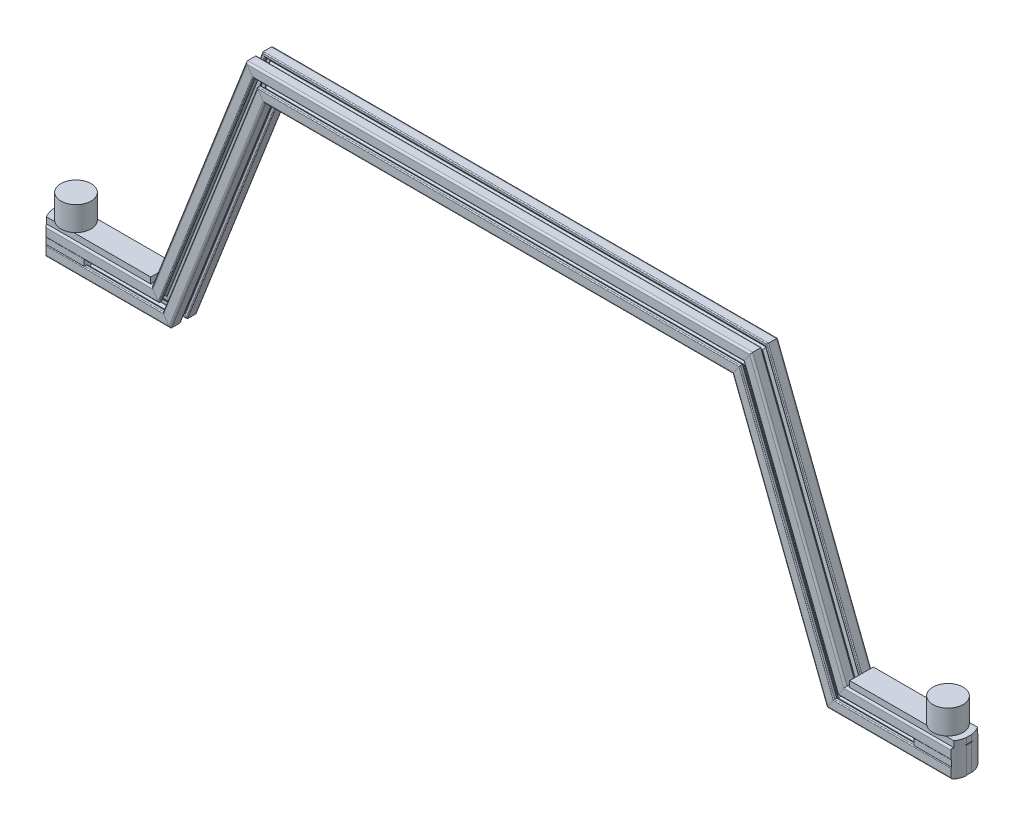
SolidWorks part; units mm, degrees
material "Commercially Pure CP-Ti UNS R50400 (SS)"
ref_plane "Front Plane" through (0, 0, 0) normal (0, 0, 1) x (1, 0, 0)
ref_plane "Top Plane" through (0, 0, 0) normal (0, 1, 0) x (1, 0, 0)
ref_plane "Right Plane" through (0, 0, 0) normal (1, 0, 0) x (0, 0, -1)
sketch "Sketch7" plane through (0, 0, 0) normal (1, 0, 0) x (0, 0, -1)
  line L0 (13.9698, 21.2743) -> (13.5298, 21.2743)
  line L1 (12.0298, 22.7743) -> (12.0298, 23.2743)
  line L2 (13.5298, 24.7743) -> (23.1398, 24.7743)
  line L3 (25.4198, 22.4943) -> (25.4198, 12.8843)
  line L4 (23.9198, 11.3843) -> (23.4198, 11.3843)
  line L5 (21.9198, 12.8843) -> (21.9198, 13.3243)
  line L6 (20.9198, 14.3243) -> (15.3498, 14.3243)
  line L7 (14.9698, 14.7043) -> (14.9698, 20.2743)
  line L8 (21.9589, -6.6897) -> (21.9589, -6.2497)
  line L9 (23.4589, -4.7497) -> (23.9589, -4.7497)
  line L10 (25.4589, -6.2497) -> (25.4589, -15.8597)
  line L11 (23.1789, -18.1397) -> (13.5689, -18.1397)
  line L12 (12.0689, -16.6397) -> (12.0689, -16.1397)
  line L13 (13.5689, -14.6397) -> (14.0089, -14.6397)
  line L14 (15.0089, -13.6397) -> (15.0089, -8.0697)
  line L15 (15.3889, -7.6897) -> (20.9589, -7.6897)
  line L16 (-6.0052, -14.6787) -> (-5.5652, -14.6787)
  line L17 (-4.0652, -16.1787) -> (-4.0652, -16.6787)
  line L18 (-5.5652, -18.1787) -> (-15.1752, -18.1787)
  line L19 (-17.4552, -15.8987) -> (-17.4552, -6.2887)
  line L20 (-15.9552, -4.7887) -> (-15.4552, -4.7887)
  line L21 (-13.9552, -6.2887) -> (-13.9552, -6.7287)
  line L22 (-12.9552, -7.7287) -> (-7.3852, -7.7287)
  line L23 (-7.0052, -8.1087) -> (-7.0052, -13.6787)
  line L24 (1.8289, -2.4886) -> (1.4132, -2.3164)
  line L25 (-1.632, 0.7289) -> (-1.8042, 1.1447)
  line L26 (-1.804, 5.4512) -> (-1.6318, 5.867)
  line L27 (1.4134, 8.9121) -> (1.8292, 9.0843)
  line L28 (6.1358, 9.0842) -> (6.5515, 8.912)
  line L29 (9.5966, 5.8667) -> (9.7688, 5.451)
  line L30 (9.7687, 1.1444) -> (9.5965, 0.7287)
  line L31 (6.5512, -2.3165) -> (6.1355, -2.4887)
  line L32 (-13.9942, 13.2853) -> (-13.9942, 12.8453)
  line L33 (-15.4942, 11.3453) -> (-15.9942, 11.3453)
  line L34 (-17.4942, 12.8453) -> (-17.4942, 22.4553)
  line L35 (-15.2142, 24.7353) -> (-5.6042, 24.7353)
  line L36 (-4.1042, 23.2353) -> (-4.1042, 22.7353)
  line L37 (-5.6042, 21.2353) -> (-6.0442, 21.2353)
  line L38 (-7.0442, 20.2353) -> (-7.0442, 14.6653)
  line L39 (-7.4242, 14.2853) -> (-12.9942, 14.2853)
  line L40 (4.9058, 11.2153) -> (4.0058, 10.7002)
  line L41 (4.0058, 10.7002) -> (3.1058, 11.2153)
  line L42 (3.1058, 11.2153) -> (-2.1975, 11.2153)
  line L43 (-2.4662, 11.3266) -> (-5.9329, 14.7933)
  line L44 (-6.0442, 15.062) -> (-6.0442, 19.3553)
  line L45 (-5.6642, 19.7353) -> (-2.5792, 19.7353)
  line L46 (-1.0592, 21.2553) -> (-1.0592, 24.2153)
  line L47 (-2.5792, 25.7353) -> (-15.4942, 25.7353)
  line L48 (-18.4942, 22.7353) -> (-18.4942, 9.8203)
  line L49 (-16.9742, 8.3003) -> (-14.0142, 8.3003)
  line L50 (-12.4942, 9.8203) -> (-12.4942, 12.9053)
  line L51 (-12.1142, 13.2853) -> (-7.8138, 13.2853)
  line L52 (-7.5451, 13.174) -> (-4.0855, 9.7144)
  line L53 (-3.9742, 9.4457) -> (-3.9742, 4.1353)
  line L54 (-3.9742, 4.1353) -> (-3.4546, 3.2353)
  line L55 (-3.4546, 3.2353) -> (-3.9742, 2.3353)
  line L56 (-3.9742, 2.3353) -> (-3.9742, -2.968)
  line L57 (-4.0855, -3.2367) -> (-7.5522, -6.7034)
  line L58 (-7.8209, -6.8147) -> (-12.1142, -6.8147)
  line L59 (-12.4942, -6.4347) -> (-12.4942, -3.3497)
  line L60 (-14.0142, -1.8297) -> (-16.9742, -1.8297)
  line L61 (-18.4942, -3.3497) -> (-18.4942, -16.2647)
  line L62 (-15.4942, -19.2647) -> (-2.5792, -19.2647)
  line L63 (-1.0592, -17.7447) -> (-1.0592, -14.7847)
  line L64 (-2.5792, -13.2647) -> (-5.6642, -13.2647)
  line L65 (-6.0442, -12.8847) -> (-6.0442, -8.5843)
  line L66 (-5.9329, -8.3156) -> (-2.4733, -4.856)
  line L67 (-2.2046, -4.7447) -> (3.1058, -4.7447)
  line L68 (3.1058, -4.7447) -> (4.0058, -4.2295)
  line L69 (4.0058, -4.2295) -> (4.9058, -4.7447)
  line L70 (4.9058, -4.7447) -> (10.2091, -4.7447)
  line L71 (10.4778, -4.856) -> (13.9445, -8.3227)
  line L72 (14.0558, -8.5914) -> (14.0558, -12.8847)
  line L73 (13.6758, -13.2647) -> (10.5908, -13.2647)
  line L74 (9.0708, -14.7847) -> (9.0708, -17.7447)
  line L75 (10.5908, -19.2647) -> (23.5058, -19.2647)
  line L76 (26.5058, -16.2647) -> (26.5058, -3.3497)
  line L77 (24.9858, -1.8297) -> (22.0258, -1.8297)
  line L78 (20.5058, -3.3497) -> (20.5058, -6.4347)
  line L79 (20.1258, -6.8147) -> (15.8254, -6.8147)
  line L80 (15.5567, -6.7034) -> (12.0971, -3.2438)
  line L81 (11.9858, -2.9751) -> (11.9858, 2.3353)
  line L82 (11.9858, 2.3353) -> (11.4662, 3.2353)
  line L83 (11.4662, 3.2353) -> (11.9858, 4.1353)
  line L84 (11.9858, 4.1353) -> (11.9858, 9.4386)
  line L85 (12.0971, 9.7073) -> (15.5638, 13.174)
  line L86 (15.8325, 13.2853) -> (20.1258, 13.2853)
  line L87 (20.5058, 12.9053) -> (20.5058, 9.8203)
  line L88 (22.0258, 8.3003) -> (24.9858, 8.3003)
  line L89 (26.5058, 9.8203) -> (26.5058, 22.7353)
  line L90 (23.5058, 25.7353) -> (10.5908, 25.7353)
  line L91 (9.0708, 24.2153) -> (9.0708, 21.2553)
  line L92 (10.5908, 19.7353) -> (13.6758, 19.7353)
  line L93 (14.0558, 19.3553) -> (14.0558, 15.0549)
  line L94 (13.9445, 14.7862) -> (10.4849, 11.3266)
  line L95 (10.2162, 11.2153) -> (4.9058, 11.2153)
  arc A0 (14.9698, 20.2743) -> (13.9698, 21.2743) centre (13.9698, 20.2743) ccw
  arc A1 (12.0298, 22.7743) -> (13.5298, 21.2743) centre (13.5298, 22.7743) ccw
  arc A2 (13.5298, 24.7743) -> (12.0298, 23.2743) centre (13.5298, 23.2743) ccw
  arc A3 (25.4198, 22.4943) -> (23.1398, 24.7743) centre (23.1398, 22.4943) ccw
  arc A4 (23.9198, 11.3843) -> (25.4198, 12.8843) centre (23.9198, 12.8843) ccw
  arc A5 (21.9198, 12.8843) -> (23.4198, 11.3843) centre (23.4198, 12.8843) ccw
  arc A6 (21.9198, 13.3243) -> (20.9198, 14.3243) centre (20.9198, 13.3243) ccw
  arc A7 (14.9698, 14.7043) -> (15.3498, 14.3243) centre (15.3498, 14.7043) ccw
  arc A8 (20.9589, -7.6897) -> (21.9589, -6.6897) centre (20.9589, -6.6897) ccw
  arc A9 (23.4589, -4.7497) -> (21.9589, -6.2497) centre (23.4589, -6.2497) ccw
  arc A10 (25.4589, -6.2497) -> (23.9589, -4.7497) centre (23.9589, -6.2497) ccw
  arc A11 (23.1789, -18.1397) -> (25.4589, -15.8597) centre (23.1789, -15.8597) ccw
  arc A12 (12.0689, -16.6397) -> (13.5689, -18.1397) centre (13.5689, -16.6397) ccw
  arc A13 (13.5689, -14.6397) -> (12.0689, -16.1397) centre (13.5689, -16.1397) ccw
  arc A14 (14.0089, -14.6397) -> (15.0089, -13.6397) centre (14.0089, -13.6397) ccw
  arc A15 (15.3889, -7.6897) -> (15.0089, -8.0697) centre (15.3889, -8.0697) ccw
  arc A16 (-7.0052, -13.6787) -> (-6.0052, -14.6787) centre (-6.0052, -13.6787) ccw
  arc A17 (-4.0652, -16.1787) -> (-5.5652, -14.6787) centre (-5.5652, -16.1787) ccw
  arc A18 (-5.5652, -18.1787) -> (-4.0652, -16.6787) centre (-5.5652, -16.6787) ccw
  arc A19 (-17.4552, -15.8987) -> (-15.1752, -18.1787) centre (-15.1752, -15.8987) ccw
  arc A20 (-15.9552, -4.7887) -> (-17.4552, -6.2887) centre (-15.9552, -6.2887) ccw
  arc A21 (-13.9552, -6.2887) -> (-15.4552, -4.7887) centre (-15.4552, -6.2887) ccw
  arc A22 (-13.9552, -6.7287) -> (-12.9552, -7.7287) centre (-12.9552, -6.7287) ccw
  arc A23 (-7.0052, -8.1087) -> (-7.3852, -7.7287) centre (-7.3852, -8.1087) ccw
  arc A24 (1.0363, -0.7421) -> (1.4132, -2.3164) centre (1.7959, -1.3925) ccw
  arc A25 (-0.0577, 0.352) -> (1.0363, -0.7421) centre (3.9823, 3.2978) ccw
  arc A26 (-1.632, 0.7289) -> (-0.0577, 0.352) centre (-0.7081, 1.1116) ccw
  arc A27 (-0.9575, 2.5244) -> (-1.8042, 1.1447) centre (-0.8803, 1.5274) ccw
  arc A28 (-0.9574, 4.0715) -> (-0.9575, 2.5244) centre (3.9823, 3.2978) ccw
  arc A29 (-1.804, 5.4512) -> (-0.9574, 4.0715) centre (-0.8802, 5.0686) ccw
  arc A30 (-0.0575, 6.2439) -> (-1.6318, 5.867) centre (-0.708, 5.4843) ccw
  arc A31 (1.0365, 7.3379) -> (-0.0575, 6.2439) centre (3.9823, 3.2978) ccw
  arc A32 (1.4134, 8.9121) -> (1.0365, 7.3379) centre (1.7961, 7.9882) ccw
  arc A33 (3.2089, 8.2376) -> (1.8292, 9.0843) centre (2.2119, 8.1604) ccw
  arc A34 (4.7561, 8.2376) -> (3.2089, 8.2376) centre (3.9823, 3.2978) ccw
  arc A35 (6.1358, 9.0842) -> (4.7561, 8.2376) centre (5.7531, 8.1603) ccw
  arc A36 (6.9284, 7.3377) -> (6.5515, 8.912) centre (6.1688, 7.9881) ccw
  arc A37 (8.0224, 6.2437) -> (6.9284, 7.3377) centre (3.9823, 3.2978) ccw
  arc A38 (9.5966, 5.8667) -> (8.0224, 6.2437) centre (8.6727, 5.484) ccw
  arc A39 (8.9222, 4.0713) -> (9.7688, 5.451) centre (8.845, 5.0683) ccw
  arc A40 (8.9221, 2.5241) -> (8.9222, 4.0713) centre (3.9823, 3.2978) ccw
  arc A41 (9.7687, 1.1444) -> (8.9221, 2.5241) centre (8.8448, 1.5271) ccw
  arc A42 (8.0222, 0.3518) -> (9.5965, 0.7287) centre (8.6726, 1.1113) ccw
  arc A43 (6.9282, -0.7422) -> (8.0222, 0.3518) centre (3.9823, 3.2978) ccw
  arc A44 (6.5512, -2.3165) -> (6.9282, -0.7422) centre (6.1685, -1.3926) ccw
  arc A45 (4.7558, -1.642) -> (6.1355, -2.4887) centre (5.7528, -1.5648) ccw
  arc A46 (3.2086, -1.642) -> (4.7558, -1.642) centre (3.9823, 3.2978) ccw
  arc A47 (1.8289, -2.4886) -> (3.2086, -1.642) centre (2.2116, -1.5647) ccw
  arc A48 (-12.9942, 14.2853) -> (-13.9942, 13.2853) centre (-12.9942, 13.2853) ccw
  arc A49 (-15.4942, 11.3453) -> (-13.9942, 12.8453) centre (-15.4942, 12.8453) ccw
  arc A50 (-17.4942, 12.8453) -> (-15.9942, 11.3453) centre (-15.9942, 12.8453) ccw
  arc A51 (-15.2142, 24.7353) -> (-17.4942, 22.4553) centre (-15.2142, 22.4553) ccw
  arc A52 (-4.1042, 23.2353) -> (-5.6042, 24.7353) centre (-5.6042, 23.2353) ccw
  arc A53 (-5.6042, 21.2353) -> (-4.1042, 22.7353) centre (-5.6042, 22.7353) ccw
  arc A54 (-6.0442, 21.2353) -> (-7.0442, 20.2353) centre (-6.0442, 20.2353) ccw
  arc A55 (-7.4242, 14.2853) -> (-7.0442, 14.6653) centre (-7.4242, 14.6653) ccw
  arc A56 (-2.4662, 11.3266) -> (-2.1975, 11.2153) centre (-2.1975, 11.5953) ccw
  arc A57 (-6.0442, 15.062) -> (-5.9329, 14.7933) centre (-5.6642, 15.062) ccw
  arc A58 (-5.6642, 19.7353) -> (-6.0442, 19.3553) centre (-5.6642, 19.3553) ccw
  arc A59 (-2.5792, 19.7353) -> (-1.0592, 21.2553) centre (-2.5792, 21.2553) ccw
  arc A60 (-1.0592, 24.2153) -> (-2.5792, 25.7353) centre (-2.5792, 24.2153) ccw
  arc A61 (-15.4942, 25.7353) -> (-18.4942, 22.7353) centre (-15.4942, 22.7353) ccw
  arc A62 (-18.4942, 9.8203) -> (-16.9742, 8.3003) centre (-16.9742, 9.8203) ccw
  arc A63 (-14.0142, 8.3003) -> (-12.4942, 9.8203) centre (-14.0142, 9.8203) ccw
  arc A64 (-12.1142, 13.2853) -> (-12.4942, 12.9053) centre (-12.1142, 12.9053) ccw
  arc A65 (-7.5451, 13.174) -> (-7.8138, 13.2853) centre (-7.8138, 12.9053) ccw
  arc A66 (-3.9742, 9.4457) -> (-4.0855, 9.7144) centre (-4.3542, 9.4457) ccw
  arc A67 (-4.0855, -3.2367) -> (-3.9742, -2.968) centre (-4.3542, -2.968) ccw
  arc A68 (-7.8209, -6.8147) -> (-7.5522, -6.7034) centre (-7.8209, -6.4347) ccw
  arc A69 (-12.4942, -6.4347) -> (-12.1142, -6.8147) centre (-12.1142, -6.4347) ccw
  arc A70 (-12.4942, -3.3497) -> (-14.0142, -1.8297) centre (-14.0142, -3.3497) ccw
  arc A71 (-16.9742, -1.8297) -> (-18.4942, -3.3497) centre (-16.9742, -3.3497) ccw
  arc A72 (-18.4942, -16.2647) -> (-15.4942, -19.2647) centre (-15.4942, -16.2647) ccw
  arc A73 (-2.5792, -19.2647) -> (-1.0592, -17.7447) centre (-2.5792, -17.7447) ccw
  arc A74 (-1.0592, -14.7847) -> (-2.5792, -13.2647) centre (-2.5792, -14.7847) ccw
  arc A75 (-6.0442, -12.8847) -> (-5.6642, -13.2647) centre (-5.6642, -12.8847) ccw
  arc A76 (-5.9329, -8.3156) -> (-6.0442, -8.5843) centre (-5.6642, -8.5843) ccw
  arc A77 (-2.2046, -4.7447) -> (-2.4733, -4.856) centre (-2.2046, -5.1247) ccw
  arc A78 (10.4778, -4.856) -> (10.2091, -4.7447) centre (10.2091, -5.1247) ccw
  arc A79 (14.0558, -8.5914) -> (13.9445, -8.3227) centre (13.6758, -8.5914) ccw
  arc A80 (13.6758, -13.2647) -> (14.0558, -12.8847) centre (13.6758, -12.8847) ccw
  arc A81 (10.5908, -13.2647) -> (9.0708, -14.7847) centre (10.5908, -14.7847) ccw
  arc A82 (9.0708, -17.7447) -> (10.5908, -19.2647) centre (10.5908, -17.7447) ccw
  arc A83 (23.5058, -19.2647) -> (26.5058, -16.2647) centre (23.5058, -16.2647) ccw
  arc A84 (26.5058, -3.3497) -> (24.9858, -1.8297) centre (24.9858, -3.3497) ccw
  arc A85 (22.0258, -1.8297) -> (20.5058, -3.3497) centre (22.0258, -3.3497) ccw
  arc A86 (20.1258, -6.8147) -> (20.5058, -6.4347) centre (20.1258, -6.4347) ccw
  arc A87 (15.5567, -6.7034) -> (15.8254, -6.8147) centre (15.8254, -6.4347) ccw
  arc A88 (11.9858, -2.9751) -> (12.0971, -3.2438) centre (12.3658, -2.9751) ccw
  arc A89 (12.0971, 9.7073) -> (11.9858, 9.4386) centre (12.3658, 9.4386) ccw
  arc A90 (15.8325, 13.2853) -> (15.5638, 13.174) centre (15.8325, 12.9053) ccw
  arc A91 (20.5058, 12.9053) -> (20.1258, 13.2853) centre (20.1258, 12.9053) ccw
  arc A92 (20.5058, 9.8203) -> (22.0258, 8.3003) centre (22.0258, 9.8203) ccw
  arc A93 (24.9858, 8.3003) -> (26.5058, 9.8203) centre (24.9858, 9.8203) ccw
  arc A94 (26.5058, 22.7353) -> (23.5058, 25.7353) centre (23.5058, 22.7353) ccw
  arc A95 (10.5908, 25.7353) -> (9.0708, 24.2153) centre (10.5908, 24.2153) ccw
  arc A96 (9.0708, 21.2553) -> (10.5908, 19.7353) centre (10.5908, 21.2553) ccw
  arc A97 (14.0558, 19.3553) -> (13.6758, 19.7353) centre (13.6758, 19.3553) ccw
  arc A98 (13.9445, 14.7862) -> (14.0558, 15.0549) centre (13.6758, 15.0549) ccw
  arc A99 (10.2162, 11.2153) -> (10.4849, 11.3266) centre (10.2162, 11.5953) ccw
sketch "Sketch1" plane through (0, 0, 0) normal (0, 0, 1) x (1, 0, 0)
  line L0 (0, 0) -> (200, 0)
  line L1 (200, 0) -> (355.8974, 400)
  line L2 (355.8974, 400) -> (755.8974, 400)
  dimension "D1" = 400
  dimension "D2" = 200
  dimension "D3" = 400
sketch "Sketch2" [suppressed] plane through (0, 0, 0) normal (1, 0, 0) x (0, 0, -1)
  line L0 (-33.5, -41) -> (-31.5, -41)
  line L1 (-31.5, -43) -> (-42, -43)
  line L2 (-43, -42) -> (-43, -31.5)
  line L3 (-41, -31.5) -> (-41, -33.5)
  line L4 (-40, -34.5) -> (-34.88, -34.5)
  line L5 (-34.5, -34.88) -> (-34.5, -40)
  line L6 (-16.657, -26.2238) -> (-18.284, -25.188)
  line L7 (-19.8123, -26.7162) -> (-18.7764, -28.3429)
  line L8 (-21.0015, -29.2647) -> (-21.4195, -27.3819)
  line L9 (-23.5808, -27.3818) -> (-23.9986, -29.2645)
  line L10 (-26.2238, -28.343) -> (-25.188, -26.716)
  line L11 (-26.7162, -25.1877) -> (-28.3429, -26.2236)
  line L12 (-29.2647, -23.9985) -> (-27.3819, -23.5805)
  line L13 (-27.3818, -21.4192) -> (-29.2645, -21.0014)
  line L14 (-28.343, -18.7762) -> (-26.716, -19.812)
  line L15 (-25.1877, -18.2838) -> (-26.2236, -16.6571)
  line L16 (-23.9985, -15.7353) -> (-23.5805, -17.6181)
  line L17 (-21.4192, -17.6182) -> (-21.0014, -15.7355)
  line L18 (-18.7762, -16.657) -> (-19.812, -18.284)
  line L19 (-18.2838, -19.8123) -> (-16.6571, -18.7764)
  line L20 (-15.7353, -21.0015) -> (-17.6181, -21.4195)
  line L21 (-17.6182, -23.5808) -> (-15.7355, -23.9986)
  line L22 (41, -33.5) -> (41, -31.5)
  line L23 (43, -31.5) -> (43, -42)
  line L24 (42, -43) -> (31.5, -43)
  line L25 (31.5, -41) -> (33.5, -41)
  line L26 (34.5, -40) -> (34.5, -34.88)
  line L27 (34.88, -34.5) -> (40, -34.5)
  line L28 (26.7162, -19.8123) -> (28.3429, -18.7764)
  line L29 (29.2647, -21.0015) -> (27.3819, -21.4195)
  line L30 (27.3818, -23.5808) -> (29.2645, -23.9986)
  line L31 (28.343, -26.2238) -> (26.716, -25.188)
  line L32 (25.1877, -26.7162) -> (26.2236, -28.3429)
  line L33 (23.9985, -29.2647) -> (23.5805, -27.3819)
  line L34 (21.4192, -27.3818) -> (21.0014, -29.2645)
  line L35 (18.7762, -28.343) -> (19.812, -26.716)
  line L36 (18.2838, -25.1877) -> (16.6571, -26.2236)
  line L37 (15.7353, -23.9985) -> (17.6181, -23.5805)
  line L38 (17.6182, -21.4192) -> (15.7355, -21.0014)
  line L39 (16.657, -18.7762) -> (18.284, -19.812)
  line L40 (19.8123, -18.2838) -> (18.7764, -16.6571)
  line L41 (21.0015, -15.7353) -> (21.4195, -17.6181)
  line L42 (23.5808, -17.6182) -> (23.9986, -15.7355)
  line L43 (26.2238, -16.657) -> (25.188, -18.284)
  line L44 (34.5, 34.88) -> (34.5, 40)
  line L45 (33.5, 41) -> (31.5, 41)
  line L46 (31.5, 43) -> (42, 43)
  line L47 (43, 42) -> (43, 31.5)
  line L48 (41, 31.5) -> (41, 33.5)
  line L49 (40, 34.5) -> (34.88, 34.5)
  line L50 (26.7162, 25.1877) -> (28.3429, 26.2236)
  line L51 (29.2647, 23.9985) -> (27.3819, 23.5805)
  line L52 (27.3818, 21.4192) -> (29.2645, 21.0014)
  line L53 (28.343, 18.7762) -> (26.716, 19.812)
  line L54 (25.1877, 18.2838) -> (26.2236, 16.6571)
  line L55 (23.9985, 15.7353) -> (23.5805, 17.6181)
  line L56 (21.4192, 17.6182) -> (21.0014, 15.7355)
  line L57 (18.7762, 16.657) -> (19.812, 18.284)
  line L58 (18.2838, 19.8123) -> (16.6571, 18.7764)
  line L59 (15.7353, 21.0015) -> (17.6181, 21.4195)
  line L60 (17.6182, 23.5808) -> (15.7355, 23.9986)
  line L61 (16.657, 26.2238) -> (18.284, 25.188)
  line L62 (19.8123, 26.7162) -> (18.7764, 28.3429)
  line L63 (21.0015, 29.2647) -> (21.4195, 27.3819)
  line L64 (23.5808, 27.3818) -> (23.9986, 29.2645)
  line L65 (26.2238, 28.343) -> (25.188, 26.716)
  line L66 (-41, 33.5) -> (-41, 31.5)
  line L67 (-43, 31.5) -> (-43, 42)
  line L68 (-42, 43) -> (-31.5, 43)
  line L69 (-31.5, 41) -> (-33.5, 41)
  line L70 (-34.5, 40) -> (-34.5, 34.88)
  line L71 (-34.88, 34.5) -> (-40, 34.5)
  line L72 (-16.657, 18.7762) -> (-18.284, 19.812)
  line L73 (-19.8123, 18.2838) -> (-18.7764, 16.6571)
  line L74 (-21.0015, 15.7353) -> (-21.4195, 17.6181)
  line L75 (-23.5808, 17.6182) -> (-23.9986, 15.7355)
  line L76 (-26.2238, 16.657) -> (-25.188, 18.284)
  line L77 (-26.7162, 19.8123) -> (-28.3429, 18.7764)
  line L78 (-29.2647, 21.0015) -> (-27.3819, 21.4195)
  line L79 (-27.3818, 23.5808) -> (-29.2645, 23.9986)
  line L80 (-28.343, 26.2238) -> (-26.716, 25.188)
  line L81 (-25.1877, 26.7162) -> (-26.2236, 28.3429)
  line L82 (-23.9985, 29.2647) -> (-23.5805, 27.3819)
  line L83 (-21.4192, 27.3818) -> (-21.0014, 29.2645)
  line L84 (-18.7762, 28.343) -> (-19.812, 26.716)
  line L85 (-18.2838, 25.1877) -> (-16.6571, 26.2236)
  line L86 (-15.7353, 23.9985) -> (-17.6181, 23.5805)
  line L87 (-17.6182, 21.4192) -> (-15.7355, 21.0014)
  line L88 (39, -10.16) -> (33.3774, -10.16)
  line L89 (31.9632, -10.7458) -> (29.8203, -12.8887)
  line L90 (29.5516, -13) -> (23.4, -13)
  line L91 (23.4, -13) -> (22.5, -13.5151)
  line L92 (22.5, -13.5151) -> (21.6, -13)
  line L93 (21.6, -13) -> (15, -13)
  line L94 (13, -15) -> (13, -21.6)
  line L95 (13, -21.6) -> (13.5196, -22.5)
  line L96 (13.5196, -22.5) -> (13, -23.4)
  line L97 (13, -23.4) -> (13, -29.5516)
  line L98 (12.8887, -29.8203) -> (11.3787, -31.3303)
  line L99 (10.5, -33.4516) -> (10.5, -40)
  line L100 (11.5, -41) -> (13.5, -41)
  line L101 (13.5, -43) -> (-13.5, -43)
  line L102 (-13.5, -41) -> (-11.5, -41)
  line L103 (-10.5, -40) -> (-10.5, -33.4516)
  line L104 (-11.3787, -31.3303) -> (-12.8887, -29.8203)
  line L105 (-13, -29.5516) -> (-13, -23.4)
  line L106 (-13, -23.4) -> (-13.5196, -22.5)
  line L107 (-13.5196, -22.5) -> (-13, -21.6)
  line L108 (-13, -21.6) -> (-13, -15)
  line L109 (-15, -13) -> (-21.6, -13)
  line L110 (-21.6, -13) -> (-22.5, -13.5151)
  line L111 (-22.5, -13.5151) -> (-23.4, -13)
  line L112 (-23.4, -13) -> (-29.5516, -13)
  line L113 (-29.8203, -12.8887) -> (-31.9632, -10.7458)
  line L114 (-33.3774, -10.16) -> (-39, -10.16)
  line L115 (-41, -12.16) -> (-41, -13.5)
  line L116 (-43, -13.5) -> (-43, 13.5)
  line L117 (-41, 13.5) -> (-41, 12.16)
  line L118 (-39, 10.16) -> (-33.3774, 10.16)
  line L119 (-31.9632, 10.7458) -> (-29.8203, 12.8887)
  line L120 (-29.5516, 13) -> (-23.4, 13)
  line L121 (-23.4, 13) -> (-22.5, 13.5151)
  line L122 (-22.5, 13.5151) -> (-21.6, 13)
  line L123 (-21.6, 13) -> (-15, 13)
  line L124 (-13, 15) -> (-13, 21.6)
  line L125 (-13, 21.6) -> (-13.5196, 22.5)
  line L126 (-13.5196, 22.5) -> (-13, 23.4)
  line L127 (-13, 23.4) -> (-13, 29.5516)
  line L128 (-12.8887, 29.8203) -> (-11.3787, 31.3303)
  line L129 (-10.5, 33.4516) -> (-10.5, 40)
  line L130 (-11.5, 41) -> (-13.5, 41)
  line L131 (-13.5, 43) -> (13.5, 43)
  line L132 (13.5, 41) -> (11.5, 41)
  line L133 (10.5, 40) -> (10.5, 33.4516)
  line L134 (11.3787, 31.3303) -> (12.8887, 29.8203)
  line L135 (13, 29.5516) -> (13, 23.4)
  line L136 (13, 23.4) -> (13.5196, 22.5)
  line L137 (13.5196, 22.5) -> (13, 21.6)
  line L138 (13, 21.6) -> (13, 15)
  line L139 (15, 13) -> (21.6, 13)
  line L140 (21.6, 13) -> (22.5, 13.5151)
  line L141 (22.5, 13.5151) -> (23.4, 13)
  line L142 (23.4, 13) -> (29.5516, 13)
  line L143 (29.8203, 12.8887) -> (31.9581, 10.7509)
  line L144 (33.3723, 10.1651) -> (39, 10.1651)
  line L145 (41, 12.1651) -> (41, 13.5)
  line L146 (43, 13.5) -> (43, -13.5)
  line L147 (41, -13.5) -> (41, -12.16)
  line L148 (45, -15.915) -> (45, 15.915)
  line L149 (43.48, 17.435) -> (40.52, 17.435)
  line L150 (39, 15.915) -> (39, 13.45)
  line L151 (38, 12.45) -> (34.9984, 12.45)
  line L152 (34.7297, 12.5613) -> (32.1113, 15.1797)
  line L153 (32, 15.4484) -> (32, 21.6)
  line L154 (32, 21.6) -> (31.4804, 22.5)
  line L155 (31.4804, 22.5) -> (32, 23.4)
  line L156 (32, 23.4) -> (32, 29.5516)
  line L157 (32.1113, 29.8203) -> (34.7297, 32.4387)
  line L158 (34.9984, 32.55) -> (38, 32.55)
  line L159 (39, 31.55) -> (39, 29.085)
  line L160 (40.52, 27.565) -> (43.48, 27.565)
  line L161 (45, 29.085) -> (45, 42)
  line L162 (42, 45) -> (29.085, 45)
  line L163 (27.565, 43.48) -> (27.565, 40.52)
  line L164 (29.085, 39) -> (31.55, 39)
  line L165 (32.55, 38) -> (32.55, 34.9984)
  line L166 (32.4387, 34.7297) -> (29.8203, 32.1113)
  line L167 (29.5516, 32) -> (23.4, 32)
  line L168 (23.4, 32) -> (22.5, 31.4849)
  line L169 (22.5, 31.4849) -> (21.6, 32)
  line L170 (21.6, 32) -> (15.4484, 32)
  line L171 (15.1797, 32.1113) -> (12.5613, 34.7297)
  line L172 (12.45, 34.9984) -> (12.45, 38)
  line L173 (13.45, 39) -> (15.915, 39)
  line L174 (17.435, 40.52) -> (17.435, 43.48)
  line L175 (15.915, 45) -> (-15.915, 45)
  line L176 (-17.435, 43.48) -> (-17.435, 40.52)
  line L177 (-15.915, 39) -> (-13.45, 39)
  line L178 (-12.45, 38) -> (-12.45, 34.9984)
  line L179 (-12.5613, 34.7297) -> (-15.1797, 32.1113)
  line L180 (-15.4484, 32) -> (-21.6, 32)
  line L181 (-21.6, 32) -> (-22.5, 31.4849)
  line L182 (-22.5, 31.4849) -> (-23.4, 32)
  line L183 (-23.4, 32) -> (-29.5516, 32)
  line L184 (-29.8203, 32.1113) -> (-32.4387, 34.7297)
  line L185 (-32.55, 34.9984) -> (-32.55, 38)
  line L186 (-31.55, 39) -> (-29.085, 39)
  line L187 (-27.565, 40.52) -> (-27.565, 43.48)
  line L188 (-29.085, 45) -> (-42, 45)
  line L189 (-45, 42) -> (-45, 29.085)
  line L190 (-43.48, 27.565) -> (-40.52, 27.565)
  line L191 (-39, 29.085) -> (-39, 31.55)
  line L192 (-38, 32.55) -> (-34.9984, 32.55)
  line L193 (-34.7297, 32.4387) -> (-32.1113, 29.8203)
  line L194 (-32, 29.5516) -> (-32, 23.4)
  line L195 (-32, 23.4) -> (-31.4804, 22.5)
  line L196 (-31.4804, 22.5) -> (-32, 21.6)
  line L197 (-32, 21.6) -> (-32, 15.4484)
  line L198 (-32.1113, 15.1797) -> (-34.7297, 12.5613)
  line L199 (-34.9984, 12.45) -> (-38, 12.45)
  line L200 (-39, 13.45) -> (-39, 15.915)
  line L201 (-40.52, 17.435) -> (-43.48, 17.435)
  line L202 (-45, 15.915) -> (-45, -15.915)
  line L203 (-43.48, -17.435) -> (-40.52, -17.435)
  line L204 (-39, -15.915) -> (-39, -13.45)
  line L205 (-38, -12.45) -> (-34.9984, -12.45)
  line L206 (-34.7297, -12.5613) -> (-32.1113, -15.1797)
  line L207 (-32, -15.4484) -> (-32, -21.6)
  line L208 (-32, -21.6) -> (-31.4804, -22.5)
  line L209 (-31.4804, -22.5) -> (-32, -23.4)
  line L210 (-32, -23.4) -> (-32, -29.5516)
  line L211 (-32.1113, -29.8203) -> (-34.7297, -32.4387)
  line L212 (-34.9984, -32.55) -> (-38, -32.55)
  line L213 (-39, -31.55) -> (-39, -29.085)
  line L214 (-40.52, -27.565) -> (-43.48, -27.565)
  line L215 (-45, -29.085) -> (-45, -42)
  line L216 (-42, -45) -> (-29.085, -45)
  line L217 (-27.565, -43.48) -> (-27.565, -40.52)
  line L218 (-29.085, -39) -> (-31.55, -39)
  line L219 (-32.55, -38) -> (-32.55, -34.9984)
  line L220 (-32.4387, -34.7297) -> (-29.8203, -32.1113)
  line L221 (-29.5516, -32) -> (-23.4, -32)
  line L222 (-23.4, -32) -> (-22.5, -31.4849)
  line L223 (-22.5, -31.4849) -> (-21.6, -32)
  line L224 (-21.6, -32) -> (-15.4484, -32)
  line L225 (-15.1797, -32.1113) -> (-12.5613, -34.7297)
  line L226 (-12.45, -34.9984) -> (-12.45, -38)
  line L227 (-13.45, -39) -> (-15.915, -39)
  line L228 (-17.435, -40.52) -> (-17.435, -43.48)
  line L229 (-15.915, -45) -> (15.915, -45)
  line L230 (17.435, -43.48) -> (17.435, -40.52)
  line L231 (15.915, -39) -> (13.45, -39)
  line L232 (12.45, -38) -> (12.45, -34.9984)
  line L233 (12.5613, -34.7297) -> (15.1797, -32.1113)
  line L234 (15.4484, -32) -> (21.6, -32)
  line L235 (21.6, -32) -> (22.5, -31.4849)
  line L236 (22.5, -31.4849) -> (23.4, -32)
  line L237 (23.4, -32) -> (29.5516, -32)
  line L238 (29.8203, -32.1113) -> (32.4387, -34.7297)
  line L239 (32.55, -34.9984) -> (32.55, -38)
  line L240 (31.55, -39) -> (29.085, -39)
  line L241 (27.565, -40.52) -> (27.565, -43.48)
  line L242 (29.085, -45) -> (42, -45)
  line L243 (45, -42) -> (45, -29.085)
  line L244 (43.48, -27.565) -> (40.52, -27.565)
  line L245 (39, -29.085) -> (39, -31.55)
  line L246 (38, -32.55) -> (34.9984, -32.55)
  line L247 (34.7297, -32.4387) -> (32.1113, -29.8203)
  line L248 (32, -29.5516) -> (32, -23.4)
  line L249 (32, -23.4) -> (31.4804, -22.5)
  line L250 (31.4804, -22.5) -> (32, -21.6)
  line L251 (32, -21.6) -> (32, -15.4484)
  line L252 (32.1113, -15.1797) -> (34.7297, -12.5613)
  line L253 (34.9984, -12.45) -> (38, -12.45)
  line L254 (39, -13.45) -> (39, -15.915)
  line L255 (40.52, -17.435) -> (43.48, -17.435)
  arc A0 (-34.5, -40) -> (-33.5, -41) centre (-33.5, -40) ccw
  arc A1 (-31.5, -43) -> (-31.5, -41) centre (-31.5, -42) ccw
  arc A2 (-43, -42) -> (-42, -43) centre (-42, -42) ccw
  arc A3 (-41, -31.5) -> (-43, -31.5) centre (-42, -31.5) ccw
  arc A4 (-41, -33.5) -> (-40, -34.5) centre (-40, -33.5) ccw
  arc A5 (-34.5, -34.88) -> (-34.88, -34.5) centre (-34.88, -34.88) ccw
  arc A6 (-15.2086, -25.7917) -> (-15.0167, -25.3284) centre (-22.5, -22.5) ccw
  arc A7 (-16.657, -26.2238) -> (-15.2086, -25.7917) centre (-16.12, -25.3802) ccw
  arc A8 (-19.8123, -26.7162) -> (-18.284, -25.188) centre (-22.5, -22.5) ccw
  arc A9 (-19.2085, -29.7915) -> (-18.7764, -28.3429) centre (-19.6199, -28.8801) ccw
  arc A10 (-19.6717, -29.9834) -> (-19.2085, -29.7915) centre (-22.5, -22.5) ccw
  arc A11 (-21.0015, -29.2647) -> (-19.6717, -29.9834) centre (-20.0253, -29.048) ccw
  arc A12 (-23.5808, -27.3818) -> (-21.4195, -27.3819) centre (-22.5, -22.5) ccw
  arc A13 (-25.3284, -29.9833) -> (-23.9986, -29.2645) centre (-24.9749, -29.0479) ccw
  arc A14 (-25.7917, -29.7914) -> (-25.3284, -29.9833) centre (-22.5, -22.5) ccw
  arc A15 (-26.2238, -28.343) -> (-25.7917, -29.7914) centre (-25.3802, -28.88) ccw
  arc A16 (-26.7162, -25.1877) -> (-25.188, -26.716) centre (-22.5, -22.5) ccw
  arc A17 (-29.7915, -25.7915) -> (-28.3429, -26.2236) centre (-28.8801, -25.3801) ccw
  arc A18 (-29.9834, -25.3283) -> (-29.7915, -25.7915) centre (-22.5, -22.5) ccw
  arc A19 (-29.2647, -23.9985) -> (-29.9834, -25.3283) centre (-29.048, -24.9747) ccw
  arc A20 (-27.3818, -21.4192) -> (-27.3819, -23.5805) centre (-22.5, -22.5) ccw
  arc A21 (-29.9833, -19.6716) -> (-29.2645, -21.0014) centre (-29.0479, -20.0251) ccw
  arc A22 (-29.7914, -19.2083) -> (-29.9833, -19.6716) centre (-22.5, -22.5) ccw
  arc A23 (-28.343, -18.7762) -> (-29.7914, -19.2083) centre (-28.88, -19.6198) ccw
  arc A24 (-25.1877, -18.2838) -> (-26.716, -19.812) centre (-22.5, -22.5) ccw
  arc A25 (-25.7915, -15.2085) -> (-26.2236, -16.6571) centre (-25.3801, -16.1199) ccw
  arc A26 (-25.3283, -15.0166) -> (-25.7915, -15.2085) centre (-22.5, -22.5) ccw
  arc A27 (-23.9985, -15.7353) -> (-25.3283, -15.0166) centre (-24.9747, -15.952) ccw
  arc A28 (-21.4192, -17.6182) -> (-23.5805, -17.6181) centre (-22.5, -22.5) ccw
  arc A29 (-19.6716, -15.0167) -> (-21.0014, -15.7355) centre (-20.0251, -15.9521) ccw
  arc A30 (-19.2083, -15.2086) -> (-19.6716, -15.0167) centre (-22.5, -22.5) ccw
  arc A31 (-18.7762, -16.657) -> (-19.2083, -15.2086) centre (-19.6198, -16.12) ccw
  arc A32 (-18.2838, -19.8123) -> (-19.812, -18.284) centre (-22.5, -22.5) ccw
  arc A33 (-15.2085, -19.2085) -> (-16.6571, -18.7764) centre (-16.1199, -19.6199) ccw
  arc A34 (-15.0166, -19.6717) -> (-15.2085, -19.2085) centre (-22.5, -22.5) ccw
  arc A35 (-15.7353, -21.0015) -> (-15.0166, -19.6717) centre (-15.952, -20.0253) ccw
  arc A36 (-17.6182, -23.5808) -> (-17.6181, -21.4195) centre (-22.5, -22.5) ccw
  arc A37 (-15.0167, -25.3284) -> (-15.7355, -23.9986) centre (-15.9521, -24.9749) ccw
  arc A38 (40, -34.5) -> (41, -33.5) centre (40, -33.5) ccw
  arc A39 (43, -31.5) -> (41, -31.5) centre (42, -31.5) ccw
  arc A40 (42, -43) -> (43, -42) centre (42, -42) ccw
  arc A41 (31.5, -41) -> (31.5, -43) centre (31.5, -42) ccw
  arc A42 (33.5, -41) -> (34.5, -40) centre (33.5, -40) ccw
  arc A43 (34.88, -34.5) -> (34.5, -34.88) centre (34.88, -34.88) ccw
  arc A44 (26.7162, -19.8123) -> (25.188, -18.284) centre (22.5, -22.5) ccw
  arc A45 (29.7915, -19.2085) -> (28.3429, -18.7764) centre (28.8801, -19.6199) ccw
  arc A46 (29.9834, -19.6717) -> (29.7915, -19.2085) centre (22.5, -22.5) ccw
  arc A47 (29.2647, -21.0015) -> (29.9834, -19.6717) centre (29.048, -20.0253) ccw
  arc A48 (27.3818, -23.5808) -> (27.3819, -21.4195) centre (22.5, -22.5) ccw
  arc A49 (29.9833, -25.3284) -> (29.2645, -23.9986) centre (29.0479, -24.9749) ccw
  arc A50 (29.7914, -25.7917) -> (29.9833, -25.3284) centre (22.5, -22.5) ccw
  arc A51 (28.343, -26.2238) -> (29.7914, -25.7917) centre (28.88, -25.3802) ccw
  arc A52 (25.1877, -26.7162) -> (26.716, -25.188) centre (22.5, -22.5) ccw
  arc A53 (25.7915, -29.7915) -> (26.2236, -28.3429) centre (25.3801, -28.8801) ccw
  arc A54 (25.3283, -29.9834) -> (25.7915, -29.7915) centre (22.5, -22.5) ccw
  arc A55 (23.9985, -29.2647) -> (25.3283, -29.9834) centre (24.9747, -29.048) ccw
  arc A56 (21.4192, -27.3818) -> (23.5805, -27.3819) centre (22.5, -22.5) ccw
  arc A57 (19.6716, -29.9833) -> (21.0014, -29.2645) centre (20.0251, -29.0479) ccw
  arc A58 (19.2083, -29.7914) -> (19.6716, -29.9833) centre (22.5, -22.5) ccw
  arc A59 (18.7762, -28.343) -> (19.2083, -29.7914) centre (19.6198, -28.88) ccw
  arc A60 (18.2838, -25.1877) -> (19.812, -26.716) centre (22.5, -22.5) ccw
  arc A61 (15.2085, -25.7915) -> (16.6571, -26.2236) centre (16.1199, -25.3801) ccw
  arc A62 (15.0166, -25.3283) -> (15.2085, -25.7915) centre (22.5, -22.5) ccw
  arc A63 (15.7353, -23.9985) -> (15.0166, -25.3283) centre (15.952, -24.9747) ccw
  arc A64 (17.6182, -21.4192) -> (17.6181, -23.5805) centre (22.5, -22.5) ccw
  arc A65 (15.0167, -19.6716) -> (15.7355, -21.0014) centre (15.9521, -20.0251) ccw
  arc A66 (15.2086, -19.2083) -> (15.0167, -19.6716) centre (22.5, -22.5) ccw
  arc A67 (16.657, -18.7762) -> (15.2086, -19.2083) centre (16.12, -19.6198) ccw
  arc A68 (19.8123, -18.2838) -> (18.284, -19.812) centre (22.5, -22.5) ccw
  arc A69 (19.2085, -15.2085) -> (18.7764, -16.6571) centre (19.6199, -16.1199) ccw
  arc A70 (19.6717, -15.0166) -> (19.2085, -15.2085) centre (22.5, -22.5) ccw
  arc A71 (21.0015, -15.7353) -> (19.6717, -15.0166) centre (20.0253, -15.952) ccw
  arc A72 (23.5808, -17.6182) -> (21.4195, -17.6181) centre (22.5, -22.5) ccw
  arc A73 (25.3284, -15.0167) -> (23.9986, -15.7355) centre (24.9749, -15.9521) ccw
  arc A74 (25.7917, -15.2086) -> (25.3284, -15.0167) centre (22.5, -22.5) ccw
  arc A75 (26.2238, -16.657) -> (25.7917, -15.2086) centre (25.3802, -16.12) ccw
  arc A76 (34.5, 34.88) -> (34.88, 34.5) centre (34.88, 34.88) ccw
  arc A77 (34.5, 40) -> (33.5, 41) centre (33.5, 40) ccw
  arc A78 (31.5, 43) -> (31.5, 41) centre (31.5, 42) ccw
  arc A79 (43, 42) -> (42, 43) centre (42, 42) ccw
  arc A80 (41, 31.5) -> (43, 31.5) centre (42, 31.5) ccw
  arc A81 (41, 33.5) -> (40, 34.5) centre (40, 33.5) ccw
  arc A82 (26.7162, 25.1877) -> (25.188, 26.716) centre (22.5, 22.5) ccw
  arc A83 (29.7915, 25.7915) -> (28.3429, 26.2236) centre (28.8801, 25.3801) ccw
  arc A84 (29.9834, 25.3283) -> (29.7915, 25.7915) centre (22.5, 22.5) ccw
  arc A85 (29.2647, 23.9985) -> (29.9834, 25.3283) centre (29.048, 24.9747) ccw
  arc A86 (27.3818, 21.4192) -> (27.3819, 23.5805) centre (22.5, 22.5) ccw
  arc A87 (29.9833, 19.6716) -> (29.2645, 21.0014) centre (29.0479, 20.0251) ccw
  arc A88 (29.7914, 19.2083) -> (29.9833, 19.6716) centre (22.5, 22.5) ccw
  arc A89 (28.343, 18.7762) -> (29.7914, 19.2083) centre (28.88, 19.6198) ccw
  arc A90 (25.1877, 18.2838) -> (26.716, 19.812) centre (22.5, 22.5) ccw
  arc A91 (25.7915, 15.2085) -> (26.2236, 16.6571) centre (25.3801, 16.1199) ccw
  arc A92 (25.3283, 15.0166) -> (25.7915, 15.2085) centre (22.5, 22.5) ccw
  arc A93 (23.9985, 15.7353) -> (25.3283, 15.0166) centre (24.9747, 15.952) ccw
  arc A94 (21.4192, 17.6182) -> (23.5805, 17.6181) centre (22.5, 22.5) ccw
  arc A95 (19.6716, 15.0167) -> (21.0014, 15.7355) centre (20.0251, 15.9521) ccw
  arc A96 (19.2083, 15.2086) -> (19.6716, 15.0167) centre (22.5, 22.5) ccw
  arc A97 (18.7762, 16.657) -> (19.2083, 15.2086) centre (19.6198, 16.12) ccw
  arc A98 (18.2838, 19.8123) -> (19.812, 18.284) centre (22.5, 22.5) ccw
  arc A99 (15.2085, 19.2085) -> (16.6571, 18.7764) centre (16.1199, 19.6199) ccw
  arc A100 (15.0166, 19.6717) -> (15.2085, 19.2085) centre (22.5, 22.5) ccw
  arc A101 (15.7353, 21.0015) -> (15.0166, 19.6717) centre (15.952, 20.0253) ccw
  arc A102 (17.6182, 23.5808) -> (17.6181, 21.4195) centre (22.5, 22.5) ccw
  arc A103 (15.0167, 25.3284) -> (15.7355, 23.9986) centre (15.9521, 24.9749) ccw
  arc A104 (15.2086, 25.7917) -> (15.0167, 25.3284) centre (22.5, 22.5) ccw
  arc A105 (16.657, 26.2238) -> (15.2086, 25.7917) centre (16.12, 25.3802) ccw
  arc A106 (19.8123, 26.7162) -> (18.284, 25.188) centre (22.5, 22.5) ccw
  arc A107 (19.2085, 29.7915) -> (18.7764, 28.3429) centre (19.6199, 28.8801) ccw
  arc A108 (19.6717, 29.9834) -> (19.2085, 29.7915) centre (22.5, 22.5) ccw
  arc A109 (21.0015, 29.2647) -> (19.6717, 29.9834) centre (20.0253, 29.048) ccw
  arc A110 (23.5808, 27.3818) -> (21.4195, 27.3819) centre (22.5, 22.5) ccw
  arc A111 (25.3284, 29.9833) -> (23.9986, 29.2645) centre (24.9749, 29.0479) ccw
  arc A112 (25.7917, 29.7914) -> (25.3284, 29.9833) centre (22.5, 22.5) ccw
  arc A113 (26.2238, 28.343) -> (25.7917, 29.7914) centre (25.3802, 28.88) ccw
  arc A114 (-40, 34.5) -> (-41, 33.5) centre (-40, 33.5) ccw
  arc A115 (-43, 31.5) -> (-41, 31.5) centre (-42, 31.5) ccw
  arc A116 (-42, 43) -> (-43, 42) centre (-42, 42) ccw
  arc A117 (-31.5, 41) -> (-31.5, 43) centre (-31.5, 42) ccw
  arc A118 (-33.5, 41) -> (-34.5, 40) centre (-33.5, 40) ccw
  arc A119 (-34.88, 34.5) -> (-34.5, 34.88) centre (-34.88, 34.88) ccw
  arc A120 (-15.2086, 19.2083) -> (-15.0167, 19.6716) centre (-22.5, 22.5) ccw
  arc A121 (-16.657, 18.7762) -> (-15.2086, 19.2083) centre (-16.12, 19.6198) ccw
  arc A122 (-19.8123, 18.2838) -> (-18.284, 19.812) centre (-22.5, 22.5) ccw
  arc A123 (-19.2085, 15.2085) -> (-18.7764, 16.6571) centre (-19.6199, 16.1199) ccw
  arc A124 (-19.6717, 15.0166) -> (-19.2085, 15.2085) centre (-22.5, 22.5) ccw
  arc A125 (-21.0015, 15.7353) -> (-19.6717, 15.0166) centre (-20.0253, 15.952) ccw
  arc A126 (-23.5808, 17.6182) -> (-21.4195, 17.6181) centre (-22.5, 22.5) ccw
  arc A127 (-25.3284, 15.0167) -> (-23.9986, 15.7355) centre (-24.9749, 15.9521) ccw
  arc A128 (-25.7917, 15.2086) -> (-25.3284, 15.0167) centre (-22.5, 22.5) ccw
  arc A129 (-26.2238, 16.657) -> (-25.7917, 15.2086) centre (-25.3802, 16.12) ccw
  arc A130 (-26.7162, 19.8123) -> (-25.188, 18.284) centre (-22.5, 22.5) ccw
  arc A131 (-29.7915, 19.2085) -> (-28.3429, 18.7764) centre (-28.8801, 19.6199) ccw
  arc A132 (-29.9834, 19.6717) -> (-29.7915, 19.2085) centre (-22.5, 22.5) ccw
  arc A133 (-29.2647, 21.0015) -> (-29.9834, 19.6717) centre (-29.048, 20.0253) ccw
  arc A134 (-27.3818, 23.5808) -> (-27.3819, 21.4195) centre (-22.5, 22.5) ccw
  arc A135 (-29.9833, 25.3284) -> (-29.2645, 23.9986) centre (-29.0479, 24.9749) ccw
  arc A136 (-29.7914, 25.7917) -> (-29.9833, 25.3284) centre (-22.5, 22.5) ccw
  arc A137 (-28.343, 26.2238) -> (-29.7914, 25.7917) centre (-28.88, 25.3802) ccw
  arc A138 (-25.1877, 26.7162) -> (-26.716, 25.188) centre (-22.5, 22.5) ccw
  arc A139 (-25.7915, 29.7915) -> (-26.2236, 28.3429) centre (-25.3801, 28.8801) ccw
  arc A140 (-25.3283, 29.9834) -> (-25.7915, 29.7915) centre (-22.5, 22.5) ccw
  arc A141 (-23.9985, 29.2647) -> (-25.3283, 29.9834) centre (-24.9747, 29.048) ccw
  arc A142 (-21.4192, 27.3818) -> (-23.5805, 27.3819) centre (-22.5, 22.5) ccw
  arc A143 (-19.6716, 29.9833) -> (-21.0014, 29.2645) centre (-20.0251, 29.0479) ccw
  arc A144 (-19.2083, 29.7914) -> (-19.6716, 29.9833) centre (-22.5, 22.5) ccw
  arc A145 (-18.7762, 28.343) -> (-19.2083, 29.7914) centre (-19.6198, 28.88) ccw
  arc A146 (-18.2838, 25.1877) -> (-19.812, 26.716) centre (-22.5, 22.5) ccw
  arc A147 (-15.2085, 25.7915) -> (-16.6571, 26.2236) centre (-16.1199, 25.3801) ccw
  arc A148 (-15.0166, 25.3283) -> (-15.2085, 25.7915) centre (-22.5, 22.5) ccw
  arc A149 (-15.7353, 23.9985) -> (-15.0166, 25.3283) centre (-15.952, 24.9747) ccw
  arc A150 (-17.6182, 21.4192) -> (-17.6181, 23.5805) centre (-22.5, 22.5) ccw
  arc A151 (-15.0167, 19.6716) -> (-15.7355, 21.0014) centre (-15.9521, 20.0251) ccw
  arc A152 (41, -12.16) -> (39, -10.16) centre (39, -12.16) ccw
  arc A153 (33.3774, -10.16) -> (31.9632, -10.7458) centre (33.3774, -12.16) ccw
  arc A154 (29.5516, -13) -> (29.8203, -12.8887) centre (29.5516, -12.62) ccw
  arc A155 (15, -13) -> (13, -15) centre (15, -15) ccw
  arc A156 (12.8887, -29.8203) -> (13, -29.5516) centre (12.62, -29.5516) ccw
  arc A157 (11.3787, -31.3303) -> (10.5, -33.4516) centre (13.5, -33.4516) ccw
  arc A158 (10.5, -40) -> (11.5, -41) centre (11.5, -40) ccw
  arc A159 (13.5, -43) -> (13.5, -41) centre (13.5, -42) ccw
  arc A160 (-13.5, -41) -> (-13.5, -43) centre (-13.5, -42) ccw
  arc A161 (-11.5, -41) -> (-10.5, -40) centre (-11.5, -40) ccw
  arc A162 (-10.5, -33.4516) -> (-11.3787, -31.3303) centre (-13.5, -33.4516) ccw
  arc A163 (-13, -29.5516) -> (-12.8887, -29.8203) centre (-12.62, -29.5516) ccw
  arc A164 (-13, -15) -> (-15, -13) centre (-15, -15) ccw
  arc A165 (-29.8203, -12.8887) -> (-29.5516, -13) centre (-29.5516, -12.62) ccw
  arc A166 (-31.9632, -10.7458) -> (-33.3774, -10.16) centre (-33.3774, -12.16) ccw
  arc A167 (-39, -10.16) -> (-41, -12.16) centre (-39, -12.16) ccw
  arc A168 (-43, -13.5) -> (-41, -13.5) centre (-42, -13.5) ccw
  arc A169 (-41, 13.5) -> (-43, 13.5) centre (-42, 13.5) ccw
  arc A170 (-41, 12.16) -> (-39, 10.16) centre (-39, 12.16) ccw
  arc A171 (-33.3774, 10.16) -> (-31.9632, 10.7458) centre (-33.3774, 12.16) ccw
  arc A172 (-29.5516, 13) -> (-29.8203, 12.8887) centre (-29.5516, 12.62) ccw
  arc A173 (-15, 13) -> (-13, 15) centre (-15, 15) ccw
  arc A174 (-12.8887, 29.8203) -> (-13, 29.5516) centre (-12.62, 29.5516) ccw
  arc A175 (-11.3787, 31.3303) -> (-10.5, 33.4516) centre (-13.5, 33.4516) ccw
  arc A176 (-10.5, 40) -> (-11.5, 41) centre (-11.5, 40) ccw
  arc A177 (-13.5, 43) -> (-13.5, 41) centre (-13.5, 42) ccw
  arc A178 (13.5, 41) -> (13.5, 43) centre (13.5, 42) ccw
  arc A179 (11.5, 41) -> (10.5, 40) centre (11.5, 40) ccw
  arc A180 (10.5, 33.4516) -> (11.3787, 31.3303) centre (13.5, 33.4516) ccw
  arc A181 (13, 29.5516) -> (12.8887, 29.8203) centre (12.62, 29.5516) ccw
  arc A182 (13, 15) -> (15, 13) centre (15, 15) ccw
  arc A183 (29.8203, 12.8887) -> (29.5516, 13) centre (29.5516, 12.62) ccw
  arc A184 (31.9581, 10.7509) -> (33.3723, 10.1651) centre (33.3723, 12.1651) ccw
  arc A185 (39, 10.1651) -> (41, 12.1651) centre (39, 12.1651) ccw
  arc A186 (43, 13.5) -> (41, 13.5) centre (42, 13.5) ccw
  arc A187 (41, -13.5) -> (43, -13.5) centre (42, -13.5) ccw
  arc A188 (45, 15.915) -> (43.48, 17.435) centre (43.48, 15.915) ccw
  arc A189 (40.52, 17.435) -> (39, 15.915) centre (40.52, 15.915) ccw
  arc A190 (38, 12.45) -> (39, 13.45) centre (38, 13.45) ccw
  arc A191 (34.7297, 12.5613) -> (34.9984, 12.45) centre (34.9984, 12.83) ccw
  arc A192 (32, 15.4484) -> (32.1113, 15.1797) centre (32.38, 15.4484) ccw
  arc A193 (32.1113, 29.8203) -> (32, 29.5516) centre (32.38, 29.5516) ccw
  arc A194 (34.9984, 32.55) -> (34.7297, 32.4387) centre (34.9984, 32.17) ccw
  arc A195 (39, 31.55) -> (38, 32.55) centre (38, 31.55) ccw
  arc A196 (39, 29.085) -> (40.52, 27.565) centre (40.52, 29.085) ccw
  arc A197 (43.48, 27.565) -> (45, 29.085) centre (43.48, 29.085) ccw
  arc A198 (45, 42) -> (42, 45) centre (42, 42) ccw
  arc A199 (29.085, 45) -> (27.565, 43.48) centre (29.085, 43.48) ccw
  arc A200 (27.565, 40.52) -> (29.085, 39) centre (29.085, 40.52) ccw
  arc A201 (32.55, 38) -> (31.55, 39) centre (31.55, 38) ccw
  arc A202 (32.4387, 34.7297) -> (32.55, 34.9984) centre (32.17, 34.9984) ccw
  arc A203 (29.5516, 32) -> (29.8203, 32.1113) centre (29.5516, 32.38) ccw
  arc A204 (15.1797, 32.1113) -> (15.4484, 32) centre (15.4484, 32.38) ccw
  arc A205 (12.45, 34.9984) -> (12.5613, 34.7297) centre (12.83, 34.9984) ccw
  arc A206 (13.45, 39) -> (12.45, 38) centre (13.45, 38) ccw
  arc A207 (15.915, 39) -> (17.435, 40.52) centre (15.915, 40.52) ccw
  arc A208 (17.435, 43.48) -> (15.915, 45) centre (15.915, 43.48) ccw
  arc A209 (-15.915, 45) -> (-17.435, 43.48) centre (-15.915, 43.48) ccw
  arc A210 (-17.435, 40.52) -> (-15.915, 39) centre (-15.915, 40.52) ccw
  arc A211 (-12.45, 38) -> (-13.45, 39) centre (-13.45, 38) ccw
  arc A212 (-12.5613, 34.7297) -> (-12.45, 34.9984) centre (-12.83, 34.9984) ccw
  arc A213 (-15.4484, 32) -> (-15.1797, 32.1113) centre (-15.4484, 32.38) ccw
  arc A214 (-29.8203, 32.1113) -> (-29.5516, 32) centre (-29.5516, 32.38) ccw
  arc A215 (-32.55, 34.9984) -> (-32.4387, 34.7297) centre (-32.17, 34.9984) ccw
  arc A216 (-31.55, 39) -> (-32.55, 38) centre (-31.55, 38) ccw
  arc A217 (-29.085, 39) -> (-27.565, 40.52) centre (-29.085, 40.52) ccw
  arc A218 (-27.565, 43.48) -> (-29.085, 45) centre (-29.085, 43.48) ccw
  arc A219 (-42, 45) -> (-45, 42) centre (-42, 42) ccw
  arc A220 (-45, 29.085) -> (-43.48, 27.565) centre (-43.48, 29.085) ccw
  arc A221 (-40.52, 27.565) -> (-39, 29.085) centre (-40.52, 29.085) ccw
  arc A222 (-38, 32.55) -> (-39, 31.55) centre (-38, 31.55) ccw
  arc A223 (-34.7297, 32.4387) -> (-34.9984, 32.55) centre (-34.9984, 32.17) ccw
  arc A224 (-32, 29.5516) -> (-32.1113, 29.8203) centre (-32.38, 29.5516) ccw
  arc A225 (-32.1113, 15.1797) -> (-32, 15.4484) centre (-32.38, 15.4484) ccw
  arc A226 (-34.9984, 12.45) -> (-34.7297, 12.5613) centre (-34.9984, 12.83) ccw
  arc A227 (-39, 13.45) -> (-38, 12.45) centre (-38, 13.45) ccw
  arc A228 (-39, 15.915) -> (-40.52, 17.435) centre (-40.52, 15.915) ccw
  arc A229 (-43.48, 17.435) -> (-45, 15.915) centre (-43.48, 15.915) ccw
  arc A230 (-45, -15.915) -> (-43.48, -17.435) centre (-43.48, -15.915) ccw
  arc A231 (-40.52, -17.435) -> (-39, -15.915) centre (-40.52, -15.915) ccw
  arc A232 (-38, -12.45) -> (-39, -13.45) centre (-38, -13.45) ccw
  arc A233 (-34.7297, -12.5613) -> (-34.9984, -12.45) centre (-34.9984, -12.83) ccw
  arc A234 (-32, -15.4484) -> (-32.1113, -15.1797) centre (-32.38, -15.4484) ccw
  arc A235 (-32.1113, -29.8203) -> (-32, -29.5516) centre (-32.38, -29.5516) ccw
  arc A236 (-34.9984, -32.55) -> (-34.7297, -32.4387) centre (-34.9984, -32.17) ccw
  arc A237 (-39, -31.55) -> (-38, -32.55) centre (-38, -31.55) ccw
  arc A238 (-39, -29.085) -> (-40.52, -27.565) centre (-40.52, -29.085) ccw
  arc A239 (-43.48, -27.565) -> (-45, -29.085) centre (-43.48, -29.085) ccw
  arc A240 (-45, -42) -> (-42, -45) centre (-42, -42) ccw
  arc A241 (-29.085, -45) -> (-27.565, -43.48) centre (-29.085, -43.48) ccw
  arc A242 (-27.565, -40.52) -> (-29.085, -39) centre (-29.085, -40.52) ccw
  arc A243 (-32.55, -38) -> (-31.55, -39) centre (-31.55, -38) ccw
  arc A244 (-32.4387, -34.7297) -> (-32.55, -34.9984) centre (-32.17, -34.9984) ccw
  arc A245 (-29.5516, -32) -> (-29.8203, -32.1113) centre (-29.5516, -32.38) ccw
  arc A246 (-15.1797, -32.1113) -> (-15.4484, -32) centre (-15.4484, -32.38) ccw
  arc A247 (-12.45, -34.9984) -> (-12.5613, -34.7297) centre (-12.83, -34.9984) ccw
  arc A248 (-13.45, -39) -> (-12.45, -38) centre (-13.45, -38) ccw
  arc A249 (-15.915, -39) -> (-17.435, -40.52) centre (-15.915, -40.52) ccw
  arc A250 (-17.435, -43.48) -> (-15.915, -45) centre (-15.915, -43.48) ccw
  arc A251 (15.915, -45) -> (17.435, -43.48) centre (15.915, -43.48) ccw
  arc A252 (17.435, -40.52) -> (15.915, -39) centre (15.915, -40.52) ccw
  arc A253 (12.45, -38) -> (13.45, -39) centre (13.45, -38) ccw
  arc A254 (12.5613, -34.7297) -> (12.45, -34.9984) centre (12.83, -34.9984) ccw
  arc A255 (15.4484, -32) -> (15.1797, -32.1113) centre (15.4484, -32.38) ccw
  arc A256 (29.8203, -32.1113) -> (29.5516, -32) centre (29.5516, -32.38) ccw
  arc A257 (32.55, -34.9984) -> (32.4387, -34.7297) centre (32.17, -34.9984) ccw
  arc A258 (31.55, -39) -> (32.55, -38) centre (31.55, -38) ccw
  arc A259 (29.085, -39) -> (27.565, -40.52) centre (29.085, -40.52) ccw
  arc A260 (27.565, -43.48) -> (29.085, -45) centre (29.085, -43.48) ccw
  arc A261 (42, -45) -> (45, -42) centre (42, -42) ccw
  arc A262 (45, -29.085) -> (43.48, -27.565) centre (43.48, -29.085) ccw
  arc A263 (40.52, -27.565) -> (39, -29.085) centre (40.52, -29.085) ccw
  arc A264 (38, -32.55) -> (39, -31.55) centre (38, -31.55) ccw
  arc A265 (34.7297, -32.4387) -> (34.9984, -32.55) centre (34.9984, -32.17) ccw
  arc A266 (32, -29.5516) -> (32.1113, -29.8203) centre (32.38, -29.5516) ccw
  arc A267 (32.1113, -15.1797) -> (32, -15.4484) centre (32.38, -15.4484) ccw
  arc A268 (34.9984, -12.45) -> (34.7297, -12.5613) centre (34.9984, -12.83) ccw
  arc A269 (39, -13.45) -> (38, -12.45) centre (38, -13.45) ccw
  arc A270 (39, -15.915) -> (40.52, -17.435) centre (40.52, -15.915) ccw
  arc A271 (43.48, -17.435) -> (45, -15.915) centre (43.48, -15.915) ccw
sweep "Sweep1" add profiles "Sketch7" path "Sketch1"
ref_plane "Plane1" through (755.8974, 0, 0) normal (1, 0, 0) x (0, 0, -1)
sketch "Sketch3" plane through (0, 25.7353, 0) normal (0, 1, 0) x (1, 0, 0)
  line L0 (0, -15.4942) -> (182.4093, -15.4942) construction
  line L1 (0, 23.5058) -> (177.9565, 23.5058)
  line L2 (0, 23.5058) -> (0, -15.4942)
  line L3 (0, -15.4942) -> (177.9565, -15.4942)
  line L4 (177.9565, 23.5058) -> (177.9565, -15.4942)
  point P6 (0, 0)
  point P7 (0, 0)
  point P8 (177.9565, -38.3202)
  point P9 (0, 16.474)
  point P10 (0, 23.5058)
  point P12 (0, -36.908)
  point P13 (0, -15.4942)
extrude "Boss-Extrude1" add sketch "Sketch3" along normal blind 10
sketch "Sketch4" plane through (0, 35.7353, 0) normal (0, 1, 0) x (1, 0, 0)
  line L0 (0, 4.0058) -> (177.9565, 4.0058) construction
  line L1 (0, 23.5058) -> (0, -15.4942) construction
  line L2 (177.9565, -15.4942) -> (177.9565, 23.5058) construction
  circle A0 centre (35, 4.0058) radius 25
  dimension "D1" = 50
  dimension "D2" = 35
extrude "Boss-Extrude2" add sketch "Sketch4" along normal blind 40
sketch "Sketch6" plane through (0, 0, 0) normal (-1, 0, 0) x (0, 0, 1)
  line L1 (-25.6271, 24.8566) -> (17.6155, 24.8566)
  line L2 (-25.6271, 24.8566) -> (-25.6271, -18.386)
  line L3 (-25.6271, -18.386) -> (17.6155, -18.386)
  line L4 (17.6155, 24.8566) -> (17.6155, -18.386)
  arc A2 (-23.5058, 25.7353) -> (-26.5058, 22.7353) centre (-23.5058, 22.7353) ccw construction
  arc A3 (15.4942, -19.2647) -> (18.4942, -16.2647) centre (15.4942, -16.2647) ccw construction
  point P4 (0, 0)
  point P5 (-25.6271, 24.8566)
  point P9 (17.6155, -18.386)
  point P10 (0, 0)
extrude "Boss-Extrude3" add sketch "Sketch6" against normal blind 70
sketch "Sketch5" plane through (0, 35.7353, 0) normal (0, 1, 0) x (1, 0, 0)
  line L0 (35, -31.2227) -> (35, -74.811)
  line L1 (35, -74.811) -> (-61.2241, -74.811)
  line L2 (-61.2241, -74.811) -> (-61.2241, 58.4921)
  line L3 (-61.2241, 58.4921) -> (35, 58.4921)
  line L4 (35, 58.4921) -> (35, 39.2343)
  arc A0 (35, 39.2343) -> (35, -31.2227) centre (35, 4.0058) ccw
extrude "Cut-Extrude1" cut sketch "Sketch5" against normal up to surface (55 mm away) up to face at (106.5839, -19.2647, 9.0367)
mirror "Mirror1" about plane through (755.8974, 0, 0) normal (1, 0, 0) of "Cut-Extrude1", "Boss-Extrude3", "Sweep1", "Boss-Extrude1", "Boss-Extrude2"
